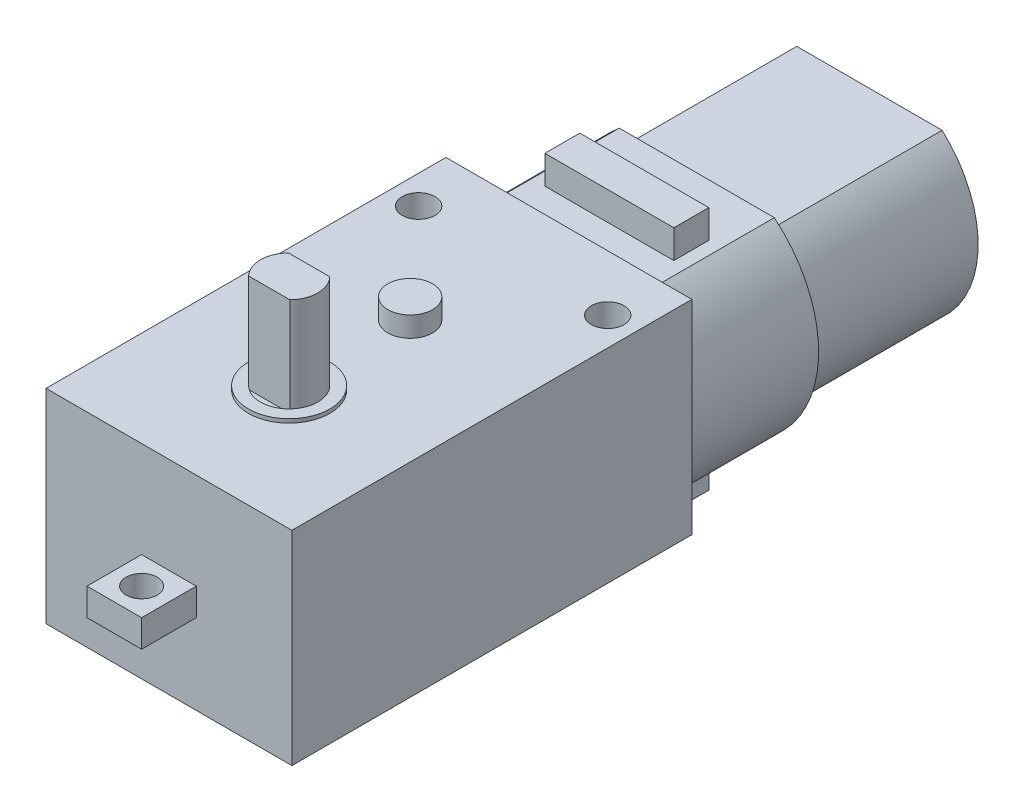
SolidWorks part; units mm, degrees
ref_plane "Front Plane" through (0, 0, 0) normal (0, 0, 1) x (1, 0, 0)
ref_plane "Top Plane" through (0, 0, 0) normal (0, 1, 0) x (1, 0, 0)
ref_plane "Right Plane" through (0, 0, 0) normal (1, 0, 0) x (0, 0, -1)
sketch "Sketch1" plane through (0, 0, 0) normal (0, 1, 0) x (1, 0, 0)
  line L0 (0, -3.725) -> (0, 13.125) construction
  line L1 (-11.25, -11) -> (11.25, -11)
  line L2 (-11.25, -11) -> (-11.25, 25.6)
  line L3 (-11.25, 25.6) -> (11.25, 25.6)
  line L4 (11.25, -11) -> (11.25, 25.6)
  line L5 (-11.25, -11) -> (11.25, 25.6) construction
  line L6 (-11.25, 25.6) -> (11.25, -11) construction
  line L8 (-11.15, 37.3) -> (11.15, 37.3)
  line L9 (-11.15, 37.3) -> (-11.15, 25.6)
  line L10 (-11.15, 25.6) -> (11.15, 25.6)
  line L11 (11.15, 37.3) -> (11.15, 25.6)
  line L12 (-11.15, 37.3) -> (11.15, 25.6) construction
  line L13 (-11.15, 25.6) -> (11.15, 37.3) construction
  line L14 (-9.7, 53.3) -> (9.7, 53.3)
  line L15 (-9.7, 53.3) -> (-9.7, 37.3)
  line L16 (-9.7, 37.3) -> (9.7, 37.3)
  line L17 (9.7, 53.3) -> (9.7, 37.3)
  line L18 (-9.7, 53.3) -> (9.7, 37.3) construction
  line L19 (-9.7, 37.3) -> (9.7, 53.3) construction
  line L26 (-1.8868, -1.825) -> (1.8868, -1.825)
  line L28 (-1.8868, 1.825) -> (1.8868, 1.825)
  line L30 (-1.8868, -1.825) -> (1.8868, 1.825) construction
  line L31 (-1.8868, 1.825) -> (1.8868, -1.825) construction
  circle A0 centre (0, 0) radius 3.725
  circle A1 centre (0, 11.075) radius 2.05
  circle A2 centre (0, 0) radius 2.625
  point P0 (0, 7.3)
  point P12 (0, 31.45)
  point P17 (0, 45.3)
  point P22 (0, 30.9)
  dimension "D3" = 11
  dimension "D4" = 7.45
  dimension "D5" = 16.85
  dimension "D6" = 4.1
  dimension "D14" = 5.25
  dimension "D1" = 36.6
  dimension "D2" = 22.5
  dimension "D7" = 22.3
  dimension "D8" = 19.4
  dimension "D9" = 11.7
  dimension "D10" = 16
  dimension "D15" = 3.65
extrude "Boss-Extrude1" add sketch "Sketch1" against normal blind 18.65 contours L4 L3 L2 L1
ref_plane "Plane2" through (0, -18.65, 0) normal (0, -1, 0) x (-1, 0, 0)
extrude "Boss-Extrude2" add sketch "Sketch1<3>" along normal blind 17.2 from surface contours L8 L11 L10 L9 starting at plane "Plane2"
sketch "Sketch1<3>" plane through (0, 0, 0) normal (0, 1, 0) x (1, 0, 0) same geometry as "Sketch1"
sketch "Sketch3" plane through (0, 0, -25.6) normal (0, 0, -1) x (-1, 0, 0)
  line L0 (11.15, -10.05) -> (-11.15, -10.05) construction
  line L1 (11.15, -1.45) -> (11.15, -18.65) construction
  line L2 (-11.15, -1.45) -> (-11.15, -18.65) construction
  line L3 (11.15, -1.45) -> (-11.15, -1.45) construction
  line L4 (11.15, -18.65) -> (-11.15, -18.65) construction
  line L5 (7.0967, -1.45) -> (-11.15, -1.45)
  line L6 (11.15, -18.65) -> (-11.15, -18.65)
  arc A0 (-7.0967, -18.65) -> (-7.0967, -1.45) centre (0, -10.05) ccw
  arc A1 (7.0967, -1.45) -> (7.0967, -18.65) centre (0, -10.05) ccw
  line M27 (-11.15, -18.65) -> (-11.15, -1.45)
  line M28 (-11.15, -1.45) -> (11.15, -1.45)
  line M29 (11.15, -1.45) -> (11.15, -18.65)
extrude "Cut-Extrude1" cut sketch "Sketch3" along normal up to next contours A0 M29 M28 | A0 L6 M29 | A1 L6 M27 | A1 M28 M27 region at (-9.9842, -3.514, -25.6) region at (9.9842, -3.514, -25.6) region at (-9.9842, -16.586, -25.6) region at (9.9842, -16.586, -25.6)
sketch "Sketch4" plane through (0, 0, -37.3) normal (0, 0, -1) x (-1, 0, 0)
  line L11 (-6.6515, -17.45) -> (6.6515, -17.45)
  line L12 (6.6515, -2.65) -> (-6.6515, -2.65)
  line L13 (-6.6515, -17.45) -> (6.6515, -17.45)
  line L14 (6.6515, -2.65) -> (-6.6515, -2.65)
  arc A7 (-6.6515, -2.65) -> (-6.6515, -17.45) centre (0, -10.05) ccw
  arc A8 (6.6515, -17.45) -> (6.6515, -2.65) centre (0, -10.05) ccw
  arc A9 (-6.6515, -2.65) -> (-6.6515, -17.45) centre (0, -10.05) ccw
  arc A10 (6.6515, -17.45) -> (6.6515, -2.65) centre (0, -10.05) ccw
  dimension "D1" = 1.2
extrude "Boss-Extrude4" add sketch "Sketch4" along normal blind 15.8 contours L13 A10 L14 A9 region at (0, -10.05, -37.3)
sketch "Sketch5" plane through (0, 0, -53.1) normal (0, 0, -1) x (-1, 0, 0)
  line L0 (9.95, -10.05) -> (-9.95, -10.05) construction
  circle A2 centre (0, -10.05) radius 1
  arc A3 (6.6515, -17.45) -> (6.6515, -2.65) centre (0, -10.05) ccw construction
  arc A4 (-6.6515, -2.65) -> (-6.6515, -17.45) centre (0, -10.05) ccw construction
  point P6 (9.95, -10.05)
  point P14 (-9.95, -10.05)
  dimension "D1" = 2
extrude "Boss-Extrude5" add sketch "Sketch5" along normal blind 1.25 contours A2
ref_plane "Plane1" through (0, -10.05, 0) normal (0, 1, 0) x (1, 0, 0)
sketch "Sketch6" plane through (0, 0, 11) normal (0, 0, 1) x (1, 0, 0)
  line L1 (-2.5, -8.8) -> (2.5, -8.8)
  line L2 (-2.5, -8.8) -> (-2.5, -11.3)
  line L3 (-2.5, -11.3) -> (2.5, -11.3)
  line L4 (2.5, -8.8) -> (2.5, -11.3)
  line L5 (-2.5, -8.8) -> (2.5, -11.3) construction
  line L6 (-2.5, -11.3) -> (2.5, -8.8) construction
  point P0 (0, -10.05)
  dimension "D1" = 5
  dimension "D2" = 2.5
extrude "Boss-Extrude6" add sketch "Sketch6" along normal blind 5
sketch "Sketch7" plane through (0, -8.8, 0) normal (0, 1, 0) x (1, 0, 0)
  line L0 (-2.5, -16) -> (-2.5, -11) construction
  line L1 (2.5, -16) -> (-2.5, -16) construction
  circle A0 centre (0, -13.5) radius 1.425
  point P4 (-2.5, -13.5)
  point P7 (0, -16)
  dimension "D1" = 2.85
extrude "Cut-Extrude2" cut sketch "Sketch7" against normal up to next
extrude "Boss-Extrude7" add sketch "Sketch1<5>" along normal blind 0.35 contours A0 A2 region at (-3.6196, 0, 0)
sketch "Sketch1<5>" plane through (0, 0, 0) normal (0, 1, 0) x (1, 0, 0) same geometry as "Sketch1"
extrude "Boss-Extrude8" add sketch "Sketch1<6>" along normal blind 1.85 contours A1 region at (0, 0, -11.075)
sketch "Sketch1<6>" plane through (0, 0, 0) normal (0, 1, 0) x (1, 0, 0) same geometry as "Sketch1"
extrude "Boss-Extrude9" add sketch "Sketch1<7>" along normal blind 9 contours L26 A2 L28 region at (0, 0, 0)
sketch "Sketch1<7>" plane through (0, 0, 0) normal (0, 1, 0) x (1, 0, 0) same geometry as "Sketch1"
sketch "Sketch8" plane through (0, -18.65, 0) normal (0, -1, 0) x (1, 0, 0)
  line L0 (10.15, -20.5) -> (11.25, -20.5) construction
  line L1 (11.25, 11) -> (11.25, -25.6) construction
  line L2 (-10.15, -20.5) -> (-11.25, -20.5) construction
  line L3 (-11.25, 11) -> (-11.25, -25.6) construction
  line L4 (-8.65, -22) -> (-8.65, -25.6) construction
  line L5 (-11.25, -25.6) -> (-7.0967, -25.6) construction
  line L6 (8.65, -22) -> (8.65, -25.6) construction
  line L8 (7.0967, -25.6) -> (11.25, -25.6) construction
  circle A0 centre (8.65, -20.5) radius 1.5
  circle A1 centre (-8.65, -20.5) radius 1.5
  dimension "D2" = 3
  dimension "D1" = 1.1
  dimension "D3" = 3.6
extrude "Cut-Extrude3" cut sketch "Sketch8" against normal up to next
sketch "Sketch10" plane through (0, -1.45, 0) normal (0, 1, 0) x (1, 0, 0)
  line L6 (-7.0967, 37.3) -> (-7.0967, 25.6) construction
  line L7 (7.0967, 37.3) -> (-7.0967, 37.3) construction
  line L8 (-5.9, 32.5) -> (5.9, 32.5)
  line L9 (5.9, 32.5) -> (5.9, 29.3)
  line L10 (-5.9, 29.3) -> (5.9, 29.3)
  line L11 (-5.9, 32.5) -> (-5.9, 29.3)
  dimension "D1" = 11.8
  dimension "D2" = 3.2
  dimension "D3" = 1.1967
  dimension "D4" = 4.8
extrude "Boss-Extrude11" add sketch "Sketch10" along normal blind 2.6
mirror "Mirror5" about plane through (0, -10.05, 0) normal (0, 1, 0) of "Boss-Extrude11"
ref_axis "Axis1" through (0, 35.3507, 0) along (0, -1, 0)
